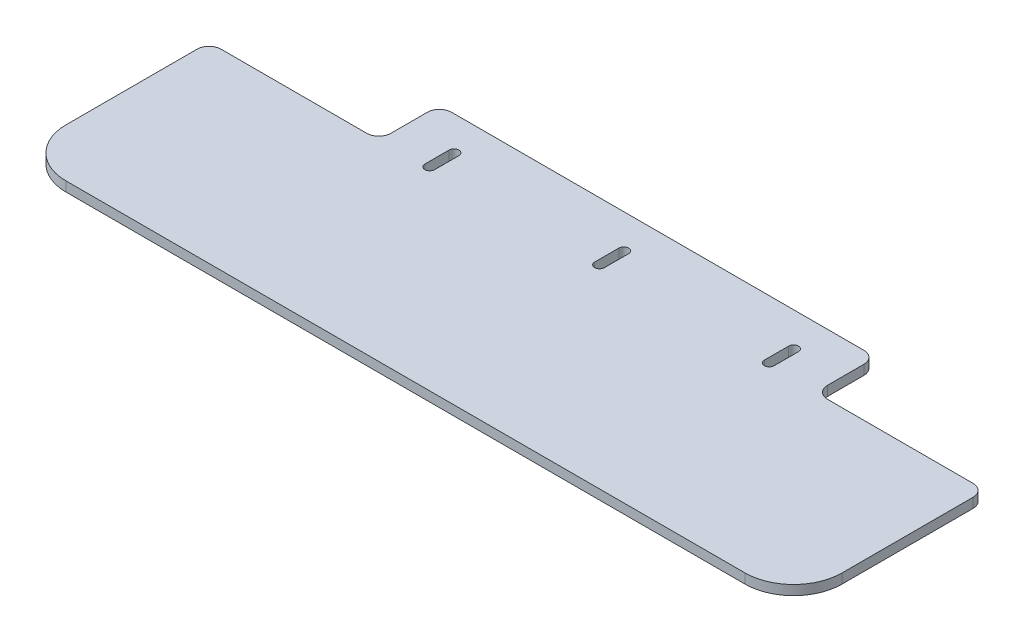
SolidWorks part; units mm, degrees
ref_plane "前视基准面" through (0, 0, 0) normal (0, 0, 1) x (1, 0, 0)
ref_plane "上视基准面" through (0, 0, 0) normal (0, 1, 0) x (1, 0, 0)
ref_plane "右视基准面" through (0, 0, 0) normal (1, 0, 0) x (0, 0, -1)
other "Configuration Table"
sketch "草图1" plane through (0, 0, 0) normal (0, 1, 0) x (1, 0, 0)
  line L1 (-140, -52) -> (140, -52)
  line L2 (-160, -32) -> (-160, 52)
  line L3 (-160, 52) -> (160, 52)
  line L4 (160, -32) -> (160, 52)
  line L5 (-160, -52) -> (160, 52) construction
  line L6 (-160, 52) -> (160, -52) construction
  arc A0 (140, -52) -> (160, -32) centre (140, -32) ccw
  arc A1 (-140, -52) -> (-160, -32) centre (-140, -32) cw
  point P0 (0, 0)
  dimension "D3" = 20
  dimension "D1" = 320
  dimension "D2" = 104
extrude "凸台-拉伸1" add sketch "草图1" along normal blind 4
sketch "草图2" plane through (0, 0, 0) normal (0, -1, 0) x (1, 0, 0)
  line L0 (-160, -27) -> (-160, -52)
  line L1 (-160, -52) -> (-160, 32) construction
  line L2 (-160, -52) -> (-90, -52)
  line L3 (160, -52) -> (-160, -52) construction
  line L4 (-90, -52) -> (-90, -27)
  line L5 (-90, -27) -> (-160, -27)
  line L6 (0, 0) -> (0, -52) construction
  line L7 (90, -27) -> (160, -27)
  line L8 (90, -52) -> (90, -27)
  line L9 (160, -52) -> (90, -52)
  line L10 (160, -27) -> (160, -52)
  line M3 (160, -52) -> (160, 32)
  line M8 (-160, -52) -> (160, -52)
  dimension "D1" = 25
  dimension "D2" = 70
extrude "切除-拉伸1" cut sketch "草图2" against normal blind 10 contours L8 L7 M8 M3 | L5 L0 L2 L4 region at (125, 0, -39.5)
fillet "圆角1" radius 5 6 edges at (90, 2, -27) (-90, 2, -27) (-160, 2, -27) (160, 2, -27) (90, 2, -52) (-90, 2, -52)
sketch "草图3" plane through (0, 4, 0) normal (0, 1, 0) x (1, 0, 0)
  line L0 (0, 38) -> (0, 28) construction
  line L3 (2.01, 38) -> (2.01, 28)
  line L6 (-2.01, 38) -> (-2.01, 28)
  line L9 (-72.01, 38) -> (-72.01, 28)
  line L10 (85, 52) -> (-85, 52) construction
  line L11 (67.99, 38) -> (67.99, 28)
  line L12 (72.01, 38) -> (72.01, 28)
  line L13 (70, 38) -> (70, 28) construction
  line L14 (-67.99, 38) -> (-67.99, 28)
  line L15 (-70, 38) -> (-70, 28) construction
  arc A6 (2.01, 38) -> (-2.01, 38) centre (0, 38) ccw
  arc A7 (-2.01, 28) -> (2.01, 28) centre (0, 28) ccw
  arc A8 (72.01, 38) -> (67.99, 38) centre (70, 38) ccw
  arc A9 (67.99, 28) -> (72.01, 28) centre (70, 28) ccw
  arc A10 (-67.99, 38) -> (-72.01, 38) centre (-70, 38) ccw
  arc A11 (-72.01, 28) -> (-67.99, 28) centre (-70, 28) ccw
  point P3 (0, 33)
  point P12 (-70, 33)
  point P16 (70, 33)
  dimension "D1" = 2.01
  dimension "D2" = 10
  dimension "D3" = 14
  dimension "D4" = 2
  dimension "D5" = 2
extrude "切除-拉伸2" cut sketch "草图3" against normal blind 10
